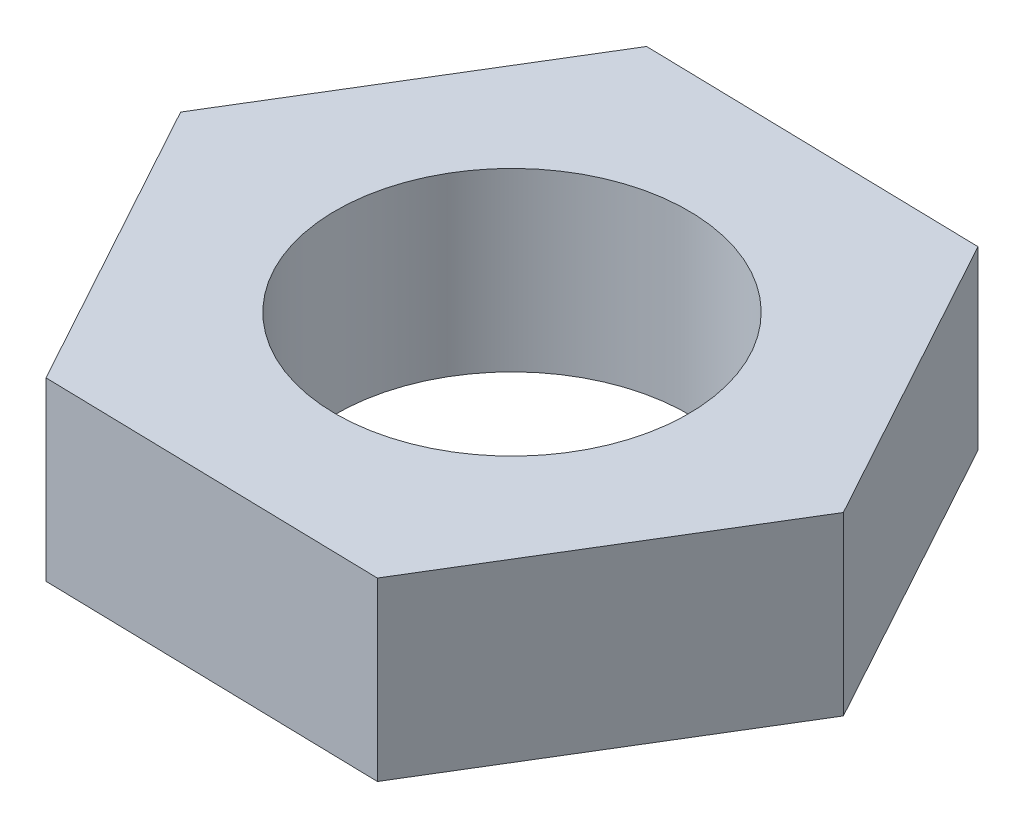
SolidWorks part; units mm, degrees
ref_plane "Plan de face" through (0, 0, 0) normal (0, 0, 1) x (1, 0, 0)
ref_plane "Plan de dessus" through (0, 0, 0) normal (0, 1, 0) x (1, 0, 0)
ref_plane "Plan de droite" through (0, 0, 0) normal (1, 0, 0) x (0, 0, -1)
sketch "Esquisse1" plane through (0, 0, 0) normal (0, 1, 0) x (1, 0, 0)
  line L1 (-19.242, 0.4376) -> (-10, -16.4452)
  line L2 (-10, -16.4452) -> (9.242, -16.8829)
  line L3 (9.242, -16.8829) -> (19.242, -0.4376)
  line L4 (19.242, -0.4376) -> (10, 16.4452)
  line L5 (10, 16.4452) -> (-9.242, 16.8829)
  line L6 (-9.242, 16.8829) -> (-19.242, 0.4376)
  circle A0 centre (0, 0) radius 16.6684 construction
  point P1 (8.536, 16.0462)
extrude "Boss.-Extru.1" add sketch "Esquisse1" along normal blind 10
sketch "Esquisse2" plane through (0, 10, 0) normal (0, 1, 0) x (1, 0, 0)
  circle A0 centre (0, 0) radius 10
  dimension "D1" = 20
extrude "Enlèv. mat.-Extru.1" cut sketch "Esquisse2" against normal blind 10
cosmetic thread "Représentation de filetage1" parameters "D2"=22
